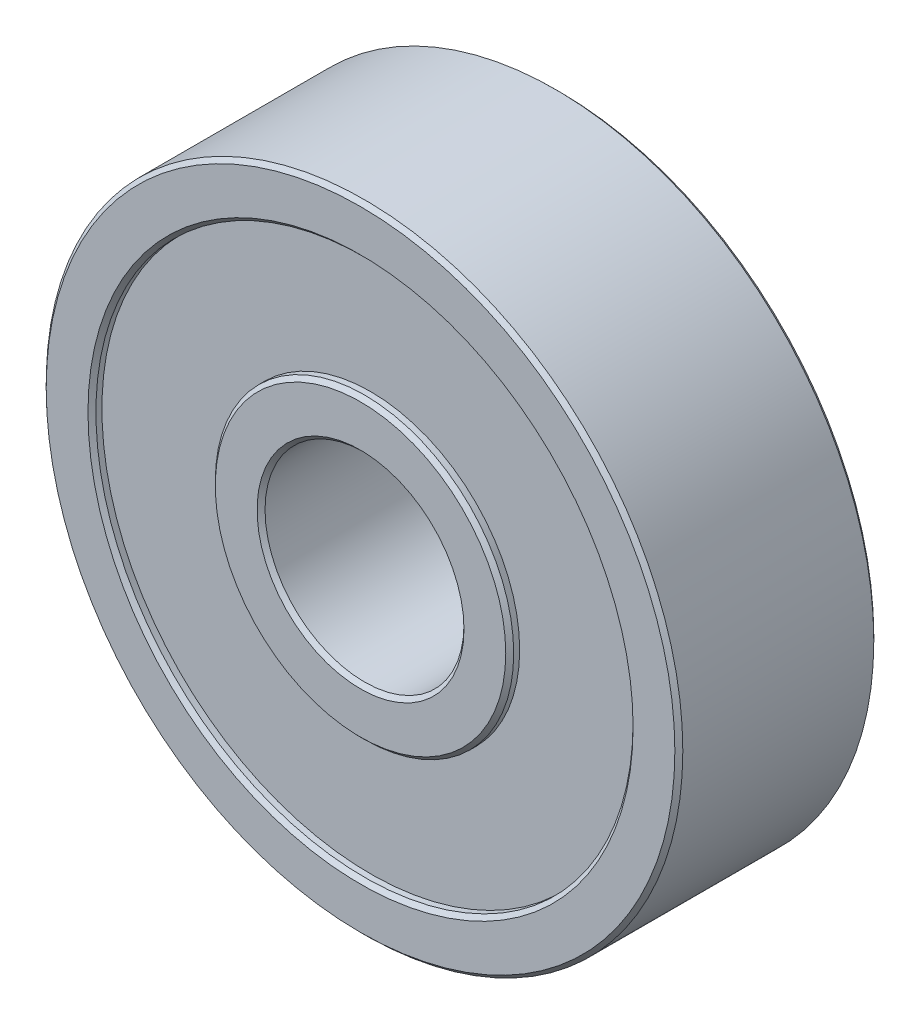
SolidWorks part; units mm, degrees
ref_plane "Front Plane" through (0, 0, 0) normal (0, 0, 1) x (1, 0, 0)
ref_plane "Top Plane" through (0, 0, 0) normal (0, 1, 0) x (1, 0, 0)
ref_plane "Right Plane" through (0, 0, 0) normal (1, 0, 0) x (0, 0, -1)
sketch "Sketch1" plane through (0, 0, 0) normal (0, 0, 1) x (1, 0, 0)
  circle A0 centre (0, 0) radius 2.5
  circle A1 centre (0, 0) radius 8
  dimension "D1" = 5
  dimension "D2" = 16
extrude "Boss-Extrude1" add sketch "Sketch1" along normal blind 2.5 and the other way blind 2.5
sketch "Sketch2" plane through (0, 0, 0) normal (0, 0, 1) x (1, 0, 0)
  circle A2 centre (0, 0) radius 3.75
  circle A3 centre (0, 0) radius 3.75
  circle A5 centre (0, 0) radius 6.75
  circle A6 centre (0, 0) radius 6.75
  dimension "D1" = 1.25
  dimension "D2" = 1.25
extrude "Cut-Extrude1" cut sketch "Sketch2" along normal blind 0.25 from surface starting at face at (2.5, 0, -2.5)
extrude "Cut-Extrude2" cut sketch "Sketch2<2>" against normal blind 0.25 from surface starting at face at (8, 0, 2.5)
sketch "Sketch2<2>" plane through (0, 0, 0) normal (0, 0, 1) x (1, 0, 0) same geometry as "Sketch2"
chamfer "Chamfer1" distance 0.1 angle 45 8 edges at (2.5, 0, -2.5) (3.75, 0, -2.5) (6.75, 0, -2.5) (8, 0, -2.5) (3.75, 0, 2.5) (2.5, 0, 2.5) (8, 0, 2.5) (6.75, 0, 2.5)
equation "\"BearingID\"=5"
equation "\"D1@Sketch1\"=\"BearingID\""
equation "\"BearingOD\"=16"
equation "\"D2@Sketch1\"=\"BearingOD\""
equation "\"BearingThickness\"=5"
equation "\"D1@Boss-Extrude1\"=\"BearingThickness\"/2"
equation "\"D2@Boss-Extrude1\"=\"BearingThickness\"/2"
